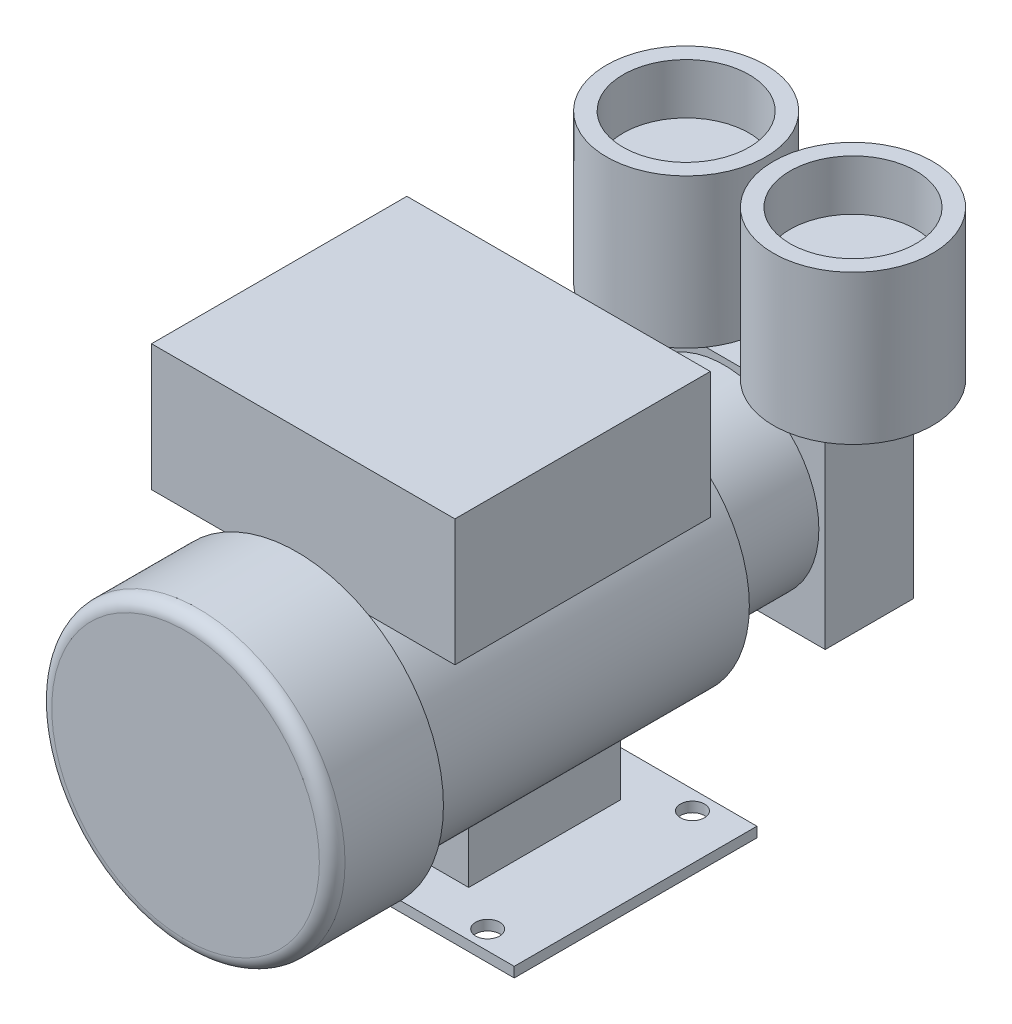
SolidWorks part; units mm, degrees
material "AISI 316 Annealed Stainless Steel Bar (SS)"
ref_plane "Front Plane" through (0, 0, 0) normal (0, 0, 1) x (1, 0, 0)
ref_plane "Top Plane" through (0, 0, 0) normal (0, 1, 0) x (1, 0, 0)
ref_plane "Right Plane" through (0, 0, 0) normal (1, 0, 0) x (0, 0, -1)
ref_plane "Plane1" through (0, 48, 0) normal (0, 1, 0) x (-1, 0, 0)
sketch "Sketch1" plane through (0, 0, 0) normal (0, 0, 1) x (1, 0, 0)
  circle A0 centre (0, 0) radius 50
  dimension "D1" = 100
extrude "Boss-Extrude1" add sketch "Sketch1" against normal blind 129
ref_plane "Motor_base_plane" through (0, -65, 0) normal (0, 1, 0) x (-1, 0, 0)
ref_axis "Axis1" through (0, 0, -144.0772) along (0, 0, 1)
sketch "Sketch2" plane through (0, -65, 0) normal (0, 1, 0) x (-1, 0, 0)
  line L0 (50, 0) -> (-50, 0) construction
  line L1 (66, -20) -> (-66, -20)
  line L2 (66, -20) -> (66, -116)
  line L3 (66, -116) -> (-66, -116)
  line L4 (-66, -20) -> (-66, -116)
  line L5 (66, -20) -> (-66, -116) construction
  line L6 (66, -116) -> (-66, -20) construction
  line L7 (0, 0) -> (0, -500.7637) construction
  line L8 (-48, -108.5) -> (48, -108.5) construction
  circle A0 centre (-48, -108.5) radius 4.75
  circle A1 centre (48, -108.5) radius 4.75
  circle A2 centre (-48, -27.5) radius 4.75
  circle A3 centre (48, -27.5) radius 4.75
  point P0 (0, -68)
  dimension "D6" = 9.5
  dimension "D10" = 81
  dimension "D1" = 20
  dimension "D2" = 132
  dimension "D3" = 96
  dimension "D4" = 48
  dimension "D5" = 40.5
  dimension "D9" = 96
  dimension "D7" = 2
  dimension "D8" = 2
extrude "Base_plate" add sketch "Sketch2" along normal blind 4 separate body
sketch "Sketch3" plane through (0, 0, -129) normal (0, 0, -1) x (-1, 0, 0)
  circle A0 centre (0, 0) radius 37.5
  dimension "D1" = 75
extrude "Motor-pump-plate" add sketch "Sketch3" along normal blind 40
sketch "Sketch18" plane through (0, 48, 0) normal (0, 1, 0) x (0, 0, -1)
  line L0 (144.0772, 0) -> (-300.4228, 0) construction
  line L2 (2.54, 60) -> (103.54, 60)
  line L3 (2.54, 60) -> (2.54, -60)
  line L4 (2.54, -60) -> (103.54, -60)
  line L5 (103.54, 60) -> (103.54, -60)
  line L6 (2.54, 60) -> (103.54, -60) construction
  line L7 (2.54, -60) -> (103.54, 60) construction
  line L8 (0, 50) -> (0, -50) construction
  point P2 (53.04, 0)
  dimension "D1" = 2.54
  dimension "D2" = 101
  dimension "D3" = 120
extrude "Electrical_box" add sketch "Sketch18" along normal blind 50
sketch "Sketch19" plane through (0, 0, 0) normal (0, 0, 1) x (1, 0, 0)
  circle A0 centre (0, 0) radius 58
  dimension "D1" = 116
extrude "Fan_shroud" add sketch "Sketch19" along normal blind 44
fillet "Fillet1" radius 5.08 1 edges at (58, 0, 44)
sketch "Sketch20" plane through (0, 0, -169) normal (0, 0, -1) x (-1, 0, 0)
  line L1 (-40, 40) -> (40, 40)
  line L2 (-40, 40) -> (-40, -40)
  line L3 (-40, -40) -> (40, -40)
  line L4 (40, 40) -> (40, -40)
  line L5 (-40, 40) -> (40, -40) construction
  line L6 (-40, -40) -> (40, 40) construction
  point P0 (0, 0)
  dimension "D1" = 80
  dimension "D2" = 80
extrude "Pump_head" add sketch "Sketch20" along normal blind 35
sketch "Sketch21" plane through (0, -61, 0) normal (0, 1, 0) x (1, 0, 0)
  line L0 (66, 20) -> (66, 116) construction
  line L1 (-30, 98) -> (30, 98)
  line L2 (-30, 98) -> (-30, 38)
  line L3 (-30, 38) -> (30, 38)
  line L4 (30, 98) -> (30, 38)
  line L5 (-30, 98) -> (30, 38) construction
  line L6 (-30, 38) -> (30, 98) construction
  line L8 (0, 116) -> (0, 16.2436) construction
  line L10 (66, 116) -> (-66, 116) construction
  line L12 (66, 68) -> (-55.5878, 68) construction
  point P0 (0, 68)
  dimension "D1" = 60
  dimension "D2" = 60
extrude "Boss-Extrude14" add sketch "Sketch21" along normal blind 25
sketch "Sketch23" plane through (0, 40, 0) normal (0, 1, 0) x (1, 0, 0)
  line L0 (-54.1417, 187) -> (51.8195, 187) construction
  line L1 (0, 204) -> (0, 162.374) construction
  line L2 (-40, 204) -> (40, 204) construction
  circle A0 centre (33, 187) radius 31.5
  circle A1 centre (-33, 187) radius 31.5
  dimension "D3" = 63
  dimension "D1" = 17
  dimension "D2" = 33
extrude "Boss-Extrude15" add sketch "Sketch23" along normal blind 59
sketch "Sketch24" plane through (0, 99, 0) normal (0, 1, 0) x (1, 0, 0)
  circle A0 centre (33, 187) radius 24.9142
  circle A1 centre (33, 187) radius 31.5 construction
  circle A2 centre (-33, 187) radius 24.9142
  circle A3 centre (-33, 187) radius 31.5 construction
extrude "Cut-Extrude1" cut sketch "Sketch24" against normal blind 20
other "CPoint1" parameters "Diameter"=50.8, "StubLength"=0
ref_axis "Axis2" through (33, 89, -187) along (0, -1, 0)
other "CPoint2" parameters "Diameter"=50.8, "StubLength"=0
ref_axis "Axis3" through (-33, 89, -187) along (0, -1, 0)
sketch "Sketch26" plane through (0, -65, 0) normal (0, -1, 0) x (1, 0, 0)
  line L1 (-66, -20) -> (66, -20)
  line L2 (-66, -20) -> (-66, -116)
  line L3 (-66, -116) -> (66, -116)
  line L4 (66, -20) -> (66, -116)
  line L5 (-66, -20) -> (66, -116) construction
  line L6 (-66, -116) -> (66, -20) construction
  point P0 (0, -68)
  point P5 (111.5666, -107.2992)
